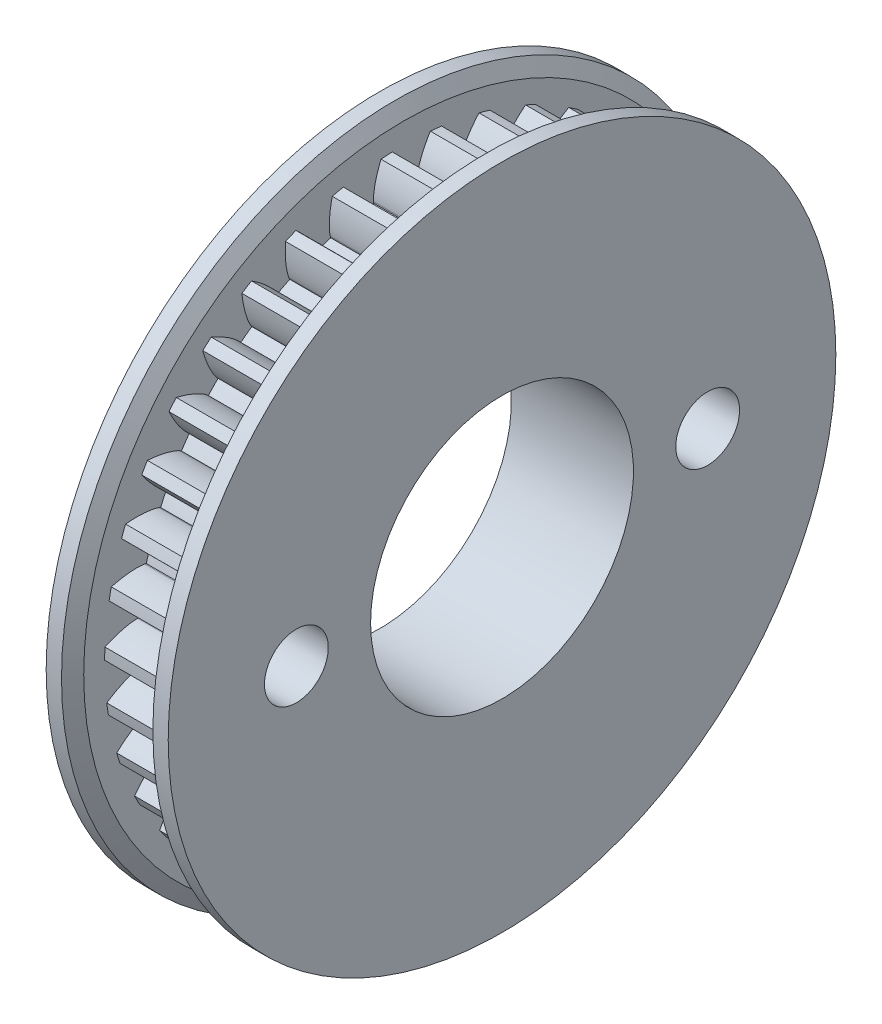
SolidWorks part; units mm, degrees
material "6061-T6 (SS)"
ref_plane "Front Plane" through (0, 0, 0) normal (1, 0, 0) x (0, 1, 0)
ref_plane "Top Plane" through (0, 0, 0) normal (0, 0, 1) x (0, 1, 0)
ref_plane "Right Plane" through (0, 0, 0) normal (0, 1, 0) x (-1, 0, 0)
sketch "Sketch1" plane through (0, 0, 0) normal (1, 0, 0) x (0, 1, 0)
  circle A0 centre (0, 0) radius 15.9155
  circle A1 centre (0, 0) radius 14.2079 construction
  circle A2 centre (0, 0) radius 14.125 construction
  circle A3 centre (0, 0) radius 15.1197 construction
  dimension "D1" = 31.831
  dimension "D2" = 28.4158
  dimension "D3" = 28.25
  dimension "D4" = 30.2394
extrude "Boss-Extrude1" add sketch "Sketch1" along normal blind 4
sketch "Sketch3" plane through (4, 0, 0) normal (1, 0, 0) x (0, 1, 0)
  line L0 (0, 0) -> (14.2079, 0) construction
  line L1 (0, 0) -> (15.118, 0.2253) construction
  line L2 (0, 0) -> (15.1144, -0.3996) construction
  line L3 (15.1144, -0.3996) -> (14.2029, -0.3755)
  line L4 (15.1144, -0.3996) -> (19.6321, -0.519)
  line L5 (19.6321, 4.279) -> (19.6321, -0.519)
  line L6 (14.2079, 0) -> (14.125, 0)
  line L7 (14.2029, -0.3755) -> (14.1201, -0.3733)
  circle A0 centre (0, 0) radius 15.1197 construction
  circle A1 centre (0, 0) radius 14.2079 construction
  circle A2 centre (0, 0) radius 14.125 construction
  arc A3 (14.125, 0) -> (14.1201, -0.3733) centre (0, 0) cw
  spline S0 degree 4 poles (14.2079, 0) (14.2184, 0.0002) (14.2478, 0.0015) (14.3034, 0.0067) (14.3936, 0.019) (14.5079, 0.0404) (14.6545, 0.0743) (14.8256, 0.1226) (15.0116, 0.1841) (15.2113, 0.26) (15.4081, 0.3438) (15.6018, 0.4346) (15.7923, 0.5316) (16.0199, 0.6567) (16.2883, 0.8171) (16.5947, 1.0196) (16.9331, 1.2666) (17.2674, 1.5362) (17.5874, 1.8161) (17.8997, 2.1149) (18.1939, 2.4154) (18.4872, 2.7431) (18.7517, 3.0537) (19.0336, 3.418) (19.257, 3.7169) (19.5356, 4.1277) (19.6953, 4.3753) (19.8765, 4.6705) (19.9539, 4.8045) (20.0017, 4.8869) knots 0 0 0 0 0 0.005377 0.015084 0.028532 0.04661 0.064855 0.092111 0.119476 0.146842 0.174209 0.201575 0.228941 0.256307 0.307035 0.361767 0.4165 0.471232 0.525964 0.580697 0.635429 0.690161 0.744894 0.799626 0.854358 0.909091 0.954545 1 1 1 1 1 construction
  spline S1 degree 4 poles (14.2079, 0) (14.2184, 0.0002) (14.2478, 0.0015) (14.3034, 0.0067) (14.3936, 0.019) (14.5079, 0.0404) (14.6545, 0.0743) (14.8256, 0.1226) (15.0116, 0.1841) (15.2113, 0.26) (15.4081, 0.3438) (15.6018, 0.4346) (15.7923, 0.5316) (16.0199, 0.6567) (16.2883, 0.8171) (16.5947, 1.0196) (16.9331, 1.2666) (17.2674, 1.5362) (17.5874, 1.8161) (17.8997, 2.1149) (18.1939, 2.4154) (18.4872, 2.7431) (18.7517, 3.0537) (19.0336, 3.418) (19.257, 3.7169) (19.4752, 4.0387) (19.5796, 4.1972) (19.6321, 4.279) knots 0 0 0 0 0 0.005377 0.015084 0.028532 0.04661 0.064855 0.092111 0.119476 0.146842 0.174209 0.201575 0.228941 0.256307 0.307035 0.361767 0.4165 0.471232 0.525964 0.580697 0.635429 0.690161 0.744894 0.799626 0.854358 0.909091 0.909091 0.909091 0.909091 0.909091
  circle M1 centre (0, 0) radius 15.9155
  dimension "D1" = 2.368
extrude "Cut-Extrude1" cut sketch "Sketch3" against normal through all contours S1 L6 A3 L3 L4 M1 region at (4, 15.178, -0.061)
mirror "Mirror1" about plane through (0, 0, 0) normal (0, 0.0264, 0.9997) of "Cut-Extrude1"
pattern_circular "CirPattern6" count 38 over 360 about axis through (4, 0, 0) along (-1, 0, 0) of "Cut-Extrude1", "Mirror1"
sketch "Sketch5" plane through (0, 0, 0) normal (0, 1, 0) x (-1, 0, 0)
  line L0 (-15.044, 0) -> (9.7198, 0) construction
  line L1 (-4, 0) -> (-5.25, 0)
  line L2 (-5.25, 0) -> (-5.25, 17.78)
  line L4 (-4, 17.03) -> (-4, 0)
  line L5 (0, 0) -> (1.25, 0)
  line L6 (0, 14.125) -> (0, -14.125) construction
  line L7 (1.25, 0) -> (1.25, 17.78)
  line L9 (0, 17.03) -> (0, 0)
  line L10 (-5.25, 17.78) -> (-4.433, 17.78)
  line L11 (-4.433, 17.78) -> (-4, 17.03)
  line L12 (0, 17.03) -> (0.433, 17.78)
  line L13 (0.433, 17.78) -> (1.25, 17.78)
  dimension "D1" = 150
  dimension "D2" = 150
  dimension "D4" = 0.75
  dimension "D5" = 1.25
  dimension "D6" = 1.25
  dimension "D3" = 17.78
revolve "Revolve1" add sketch "Sketch5" angle 360 about L0
sketch "Sketch6" plane through (-1.25, 0, 0) normal (-1, 0, 0) x (0, -1, 0)
  circle A0 centre (0, 0) radius 7
  dimension "D1" = 14
extrude "Cut-Extrude2" cut sketch "Sketch6" against normal through all
sketch "Sketch7" plane through (0, 0, 0) normal (1, 0, 0) x (0, 1, 0)
  line L0 (0, -10.9537) -> (0, 10.9537) construction
  circle A0 centre (0, 10.9537) radius 1.5
  circle A1 centre (0, -10.9537) radius 1.5
  point P5 (0, 0)
  dimension "D2" = 21.9075
hole_wizard "M3 Clearance Hole1" positions "Sketch8" profile "Sketch9" hole size "M3" standard "ANSI Metric"
sketch "Sketch8" plane through (-1.25, 0, 0) normal (-1, 0, 0) x (0, 0, 1)
  point P0 (10.9537, 0)
  point P3 (-10.9537, 0)
sketch "Sketch9" plane through (-1.25, 0, 10.9537) normal (0, 1, 0) x (0, 0, 1)
  line L0 (0, 0) -> (0, 26.4215)
  line L1 (0, 26.4215) -> (1.7, 25.4)
  line L2 (1.7, 25.4) -> (1.7, 0)
  line L5 (1.7, 0) -> (0, 0)
  line L10 (0, 26.4215) -> (-1.7, 25.4) construction
  line L11 (0, -6.35) -> (0, 107.95) construction
  dimension "Hole Dia." = 3.4
  dimension "Hole Depth" = 25.4
  dimension "Drill Angle" = 118
equation "\"DiametralPitch\"= pi / \"Pitch\""
equation "\"NumberTeeth\"= 38"
equation "\"PressureAngle\"= 20"
equation "\"PitchDiameter\"= \"NumberTeeth\" / \"DiametralPitch\""
equation "\"BaseDiameter\"= \"PitchDiameter\" * cos ( \"PressureAngle\" )"
equation "\"Addendum\"= 1 / \"DiametralPitch\""
equation "\"Dedendum\"= 1.25 / \"DiametralPitch\""
equation "\"AddendumDiameter\"= \"PitchDiameter\" + \"Addendum\" + \"Addendum\""
equation "\"DedendumDiameter\"= \"PitchDiameter\" - \"Dedendum\" - \"Dedendum\""
equation "\"ToothSpacing\"= 360 / ( 4 * \"NumberTeeth\" )"
equation "\"D1@Sketch1\"=\"AddendumDiameter\""
equation "\"D2@Sketch1\"=\"BaseDiameter\""
equation "\"D3@Sketch1\"=\"DedendumDiameter\""
equation "\"D4@Sketch1\"=\"PitchDiameter\""
equation "\"D1@Sketch3\"=\"ToothSpacing\""
equation "\"D1@CirPattern6\"=\"NumberTeeth\""
equation "\"Pitch\"= 2.5"
equation "\"D2@Sketch7\"=0.8625in"
equation "\"D3@Sketch5\"=0.7in"
